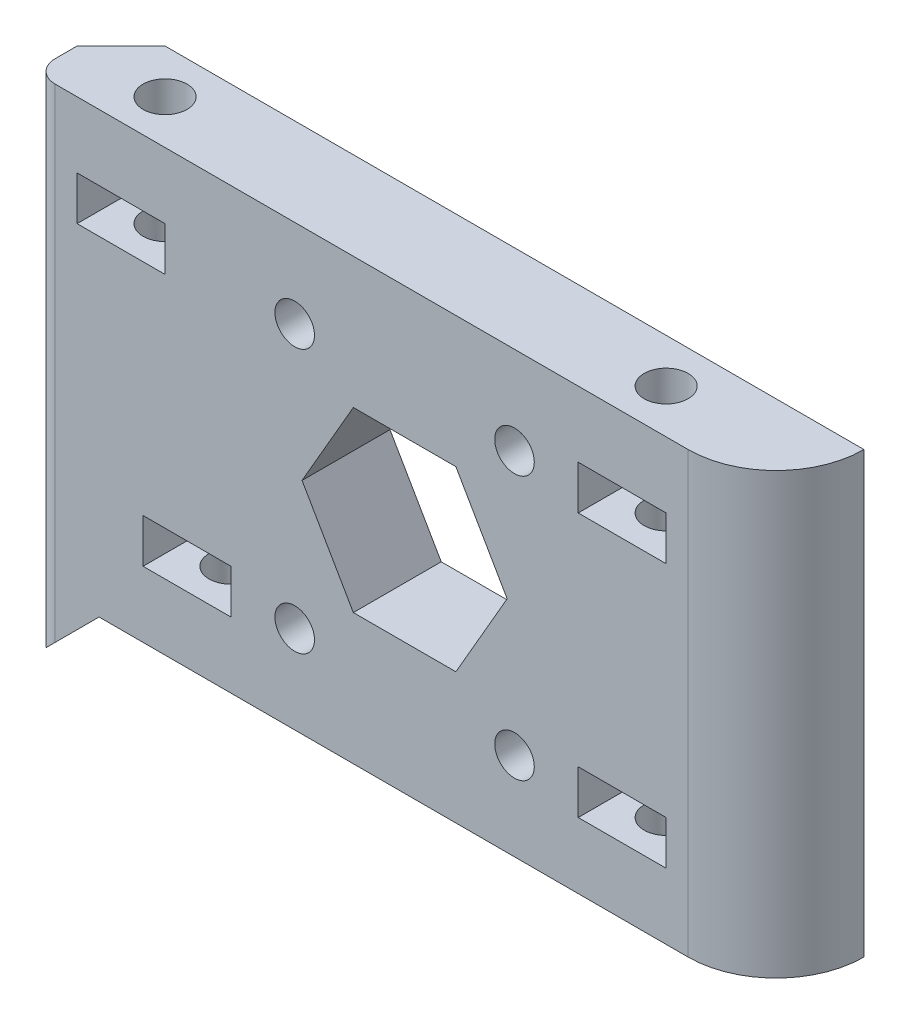
SolidWorks part; units mm, degrees
ref_plane "Front Plane" through (0, 0, 0) normal (0, 0, 1) x (1, 0, 0)
ref_plane "Top Plane" through (0, 0, 0) normal (0, 1, 0) x (1, 0, 0)
ref_plane "Right Plane" through (0, 0, 0) normal (1, 0, 0) x (0, 0, -1)
sketch "Sketch1" plane through (0, 0, 0) normal (0, 0, 1) x (1, 0, 0)
  line L0 (-9.3359, -18.2969) -> (-6.3359, -15.2969)
  line L1 (-9.3359, 4.7031) -> (24.4641, 4.7031)
  line L2 (-9.3359, 4.7031) -> (-9.3359, -15.2969)
  line L3 (-9.3359, -15.2969) -> (24.4641, -15.2969)
  line L4 (24.4641, 4.7031) -> (24.4641, -15.2969)
  line L5 (12.2298, -5.2969) -> (9.8969, -1.2564)
  line L6 (9.8969, -1.2564) -> (5.2313, -1.2564)
  line L7 (5.2313, -1.2564) -> (2.8984, -5.2969)
  line L8 (2.8984, -5.2969) -> (5.2313, -9.3375)
  line L9 (5.2313, -9.3375) -> (9.8969, -9.3375)
  line L10 (9.8969, -9.3375) -> (12.2298, -5.2969)
  line L35 (-9.3359, -15.2969) -> (-6.3359, -15.2969)
  line L36 (-9.3359, -15.2969) -> (-9.3359, -18.2969)
  line L37 (-9.3359, -18.2969) -> (-6.3359, -18.2969)
  line L38 (-6.3359, -15.2969) -> (-6.3359, -18.2969)
  line L40 (-4.3359, -10.2969) -> (-0.3359, -10.2969)
  line L41 (-4.3359, -10.2969) -> (-4.3359, -12.2969)
  line L42 (-4.3359, -12.2969) -> (-0.3359, -12.2969)
  line L43 (-0.3359, -10.2969) -> (-0.3359, -12.2969)
  line L44 (15.4641, -10.2969) -> (19.4641, -10.2969)
  line L45 (15.4641, -10.2969) -> (15.4641, -12.2969)
  line L46 (15.4641, -12.2969) -> (19.4641, -12.2969)
  line L47 (19.4641, -10.2969) -> (19.4641, -12.2969)
  line L48 (15.4641, 1.7031) -> (19.4641, 1.7031)
  line L49 (15.4641, 1.7031) -> (15.4641, -0.2969)
  line L50 (15.4641, -0.2969) -> (19.4641, -0.2969)
  line L51 (19.4641, 1.7031) -> (19.4641, -0.2969)
  line L52 (-7.3359, 1.7031) -> (-3.3359, 1.7031)
  line L53 (-7.3359, 1.7031) -> (-7.3359, -0.2969)
  line L54 (-7.3359, -0.2969) -> (-3.3359, -0.2969)
  line L55 (-3.3359, 1.7031) -> (-3.3359, -0.2969)
  circle A0 centre (7.5641, -5.2969) radius 4.0406 construction
  circle A1 centre (2.5641, -11.2969) radius 0.9
  circle A2 centre (12.5641, -11.2969) radius 0.9
  circle A3 centre (2.5641, 0.7031) radius 0.9
  circle A4 centre (12.5641, 0.7031) radius 0.9
  point P17 (17.4641, -12.2969)
  point P25 (-5.3359, 1.7031)
  point P26 (17.4641, 1.7031)
  point P51 (-2.3359, -12.2969)
  dimension "D23" = 5
  dimension "D24" = 5
  dimension "D1" = 33.8
  dimension "D2" = 20
  dimension "D3" = 10
  dimension "D4" = 16.9
  dimension "D5" = 4
  dimension "D6" = 2
  dimension "D7" = 3
  dimension "D8" = 7
  dimension "D9" = 3
  dimension "D10" = 4
  dimension "D11" = 2
  dimension "D12" = 4
  dimension "D13" = 2
  dimension "D14" = 4
  dimension "D15" = 7
  dimension "D16" = 3
  dimension "D17" = 3
  dimension "D18" = 3
  dimension "D19" = 7
  dimension "D20" = 2
  dimension "D21" = 4
  dimension "D22" = 3
  dimension "D25" = 5
  dimension "D26" = 5
  dimension "D27" = 4
  dimension "D28" = 4
  dimension "D29" = 4
  dimension "D30" = 4
extrude "Boss-Extrude1" add sketch "Sketch1" along normal blind 4 contours L4 L1 L2 L3 L46 L50 L10 L9 L8 L7 L6 L5 | L3 L36 L0 region at (-8.3359, -16.2969, 0) region at (-7.8359, -14.9042, 0)
sketch "Sketch3" plane through (0, -15.2969, 0) normal (0, -1, 0) x (1, 0, 0)
  line L1 (24.4641, 0) -> (-9.3359, 0)
  line L3 (24.4641, 4) -> (-9.3359, 4)
  line L4 (-9.3359, 0) -> (-9.3359, 4)
  circle A0 centre (17.4641, 2) radius 1
  circle A1 centre (-2.3359, 2) radius 1
  dimension "D2" = 7
  dimension "D3" = 2
  dimension "D4" = 2
extrude "Cut-Extrude1" cut sketch "Sketch3" against normal blind 20 contours A0 region at (17.4641, -15.2969, 2)
extrude "Cut-Extrude2" cut sketch "Sketch3<3>" against normal blind 10 contours A1 region at (-2.3359, -15.2969, 2)
sketch "Sketch3<3>" plane through (0, -15.2969, 0) normal (0, -1, 0) x (1, 0, 0) same geometry as "Sketch3"
sketch "Sketch5" plane through (0, 4.7031, 0) normal (0, 1, 0) x (1, 0, 0)
  line L0 (-9.3359, 0) -> (-9.3359, -4)
  circle A0 centre (-5.3359, -2) radius 1
  point P6 (0, 0)
  point P7 (0, 0)
  point P8 (0, 0)
  dimension "D2" = 2
  dimension "D1" = 4
extrude "Cut-Extrude3" cut sketch "Sketch5" against normal blind 10 contours A0 region at (-5.3359, 4.7031, 2)
chamfer "Chamfer2" distance 2 angle 45 1 edges at (-9.3359, -6.7969, 0)
fillet "Fillet2" radius 1 1 edges at (-9.3359, -6.7969, 4)
fillet "Fillet3" radius 4 1 edges at (24.4641, -5.2969, 4)
